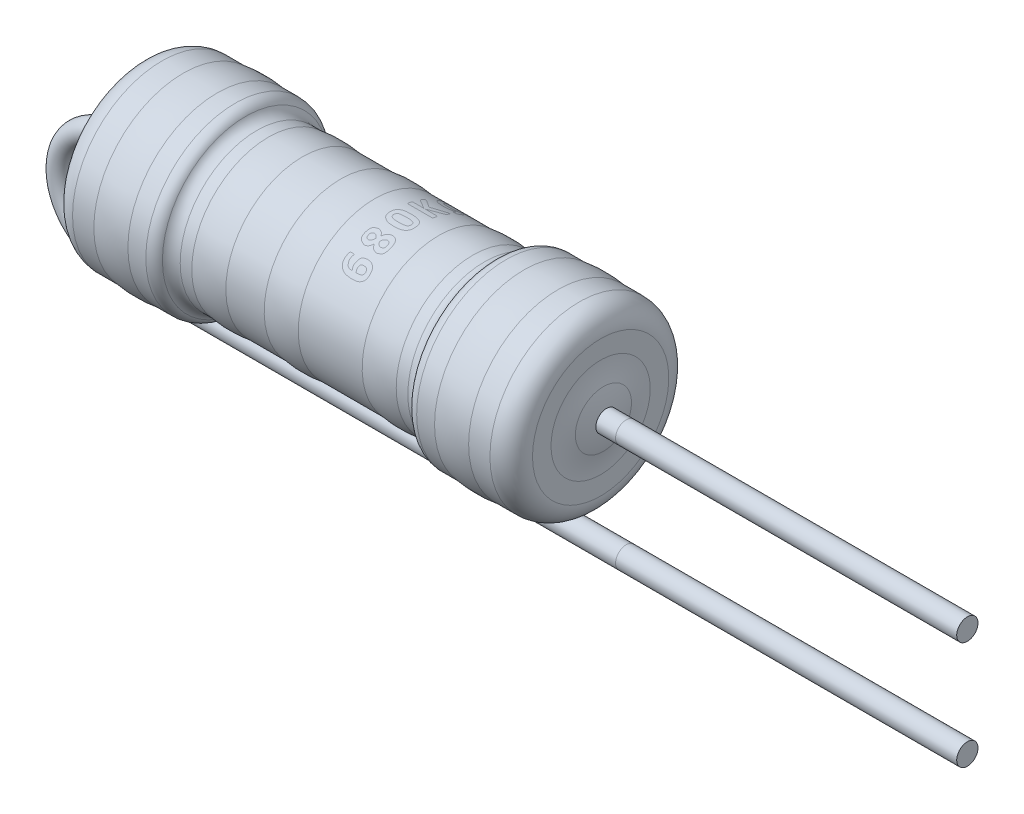
SolidWorks part; units mm, degrees
ref_plane "Front Plane" through (0, 0, 0) normal (0, 0, 1) x (1, 0, 0)
ref_plane "Top Plane" through (0, 0, 0) normal (0, 1, 0) x (1, 0, 0)
ref_plane "Right Plane" through (0, 0, 0) normal (1, 0, 0) x (0, 0, -1)
sketch "Sketch Set Wire Width" plane through (0, 0, 0) normal (0, 0, 1) x (1, 0, 0)
  line L0 (0, 0) -> (6, 0)
  line L1 (6, -2.54) -> (-6, -2.54)
  line L2 (6, 0) -> (14.0102, 0)
  line L3 (-6, 0) -> (-6, -2.54) construction
  line L4 (-6, 0) -> (-6, -2.54) construction
  line L5 (6, -2.54) -> (6, 0) construction
  line L6 (6, -2.54) -> (14.0102, -2.54)
  line L7 (14.0102, -2.54) -> (14.0102, 0) construction
  line L8 (-6, 0) -> (0, 0)
  arc A0 (-6, 0) -> (-6, -2.54) centre (-6, -1.27) ccw
  dimension "D2" = 2.54
  dimension "D3" = 30
  dimension "D1" = 12
  dimension "D4" = 6
sketch "Sketch Wire Diameter" plane through (0, 0, 0) normal (1, 0, 0) x (0, 0, -1)
  circle A0 centre (0, 0) radius 0.25
  dimension "D1" = 0.5
sweep "SET WIRE LENGTH" add profiles "Sketch Wire Diameter" path "Sketch Set Wire Width"
sketch "Sketch3" plane through (0, 0, 0) normal (0, 0, 1) x (1, 0, 0)
  line L0 (-5.4, 0) -> (5.4, 0)
  line L1 (0, 0) -> (0, 1.8) construction
  line L2 (-2.9, 1.8) -> (2.9, 1.8)
  line L3 (-5.4, 0) -> (-5.4, 1.6)
  line L4 (-4.9, 2.1) -> (-3.18, 2.1)
  line L5 (-2.9, 1.82) -> (-2.9, 1.8)
  line L6 (5.4, 0) -> (5.4, 1.6)
  line L7 (4.9, 2.1) -> (3.18, 2.1)
  line L8 (2.9, 1.82) -> (2.9, 1.8)
  arc A0 (-5.4, 1.6) -> (-4.9, 2.1) centre (-4.9, 1.6) cw
  arc A1 (5.4, 1.6) -> (4.9, 2.1) centre (4.9, 1.6) ccw
  arc A2 (-3.18, 2.1) -> (-2.9, 1.82) centre (-3.18, 1.82) cw
  arc A3 (3.18, 2.1) -> (2.9, 1.82) centre (3.18, 1.82) ccw
  dimension "D5" = 0.5
  dimension "D6" = 0.28
  dimension "D1" = 10.8
  dimension "D2" = 5.8
  dimension "D3" = 1.8
  dimension "D4" = 2.1
revolve "Revolve2" add sketch "Sketch3" angle 360 about L0
fillet "Fillet1" radius 0.3 2 edges at (2.9, 0, 1.8) (-2.9, 0, 1.8)
sketch "Sketch5" plane through (0, 0, 0) normal (0, 0, 1) x (1, 0, 0)
  line L0 (0, 0) -> (2, 0) construction
  line L1 (0, 0) -> (-0.3, 0) construction
  line L2 (-0.3, 0) -> (-2, 0) construction
  line L3 (-2, 0) -> (-4, 0) construction
  line L4 (2, 0) -> (4, 0) construction
  line L5 (-4, 0) -> (-4, 2.1) construction
  line L6 (-0.3, 0) -> (-0.3, 1.8) construction
  line L7 (-2, 0) -> (-2, 1.8) construction
  line L8 (2, 0) -> (2, 1.8) construction
  line L9 (4, 0) -> (4, 2.1) construction
  line L10 (-4, 2.1) -> (-4, 2.13) construction
  line L11 (-4.9, 2.1) -> (-3.18, 2.1) construction
  line L12 (4.9, 2.1) -> (3.18, 2.1) construction
  line L13 (-2.9, 1.8) -> (2.9, 1.8) construction
  line L14 (-2, 1.8) -> (-2, 1.83) construction
  line L17 (-4.4, 2.1) -> (-3.6, 2.1)
  line L19 (-5.4, 0) -> (5.4, 0) construction
  line L22 (-2.4, 1.8) -> (-1.6, 1.8) construction
  line L26 (-0.7, 1.8) -> (0.1, 1.8) construction
  line L30 (1.6, 1.8) -> (2.4, 1.8) construction
  line L34 (3.6, 2.1) -> (4.4, 2.1) construction
  line L36 (-0.3, 1.8) -> (-0.3, 1.83) construction
  line L37 (2, 1.8) -> (2, 1.83) construction
  line L38 (4, 2.1) -> (4, 2.13) construction
  arc A0 (-4.4, 2.1) -> (-3.6, 2.1) centre (-4, -0.5517) cw
  arc A1 (-2.4, 1.8) -> (-1.6, 1.8) centre (-2, -0.8517) cw construction
  arc A2 (-0.7, 1.8) -> (0.1, 1.8) centre (-0.3, -0.8517) cw construction
  arc A3 (1.6, 1.8) -> (2.4, 1.8) centre (2, -0.8517) cw construction
  arc A4 (3.6, 2.1) -> (4.4, 2.1) centre (4, -0.5517) cw construction
  dimension "D3" = 0.8
  dimension "D1" = 4
  dimension "D2" = 4
  dimension "D4" = 0.03
  dimension "D5" = 2
  dimension "D6" = 2
  dimension "D7" = 1.7
revolve "Band 1" add sketch "Sketch5" angle 360 about L2
sketch "Sketch8" plane through (0, 0, 0) normal (0, 0, 1) x (1, 0, 0)
  line L0 (-2.4, 1.8) -> (-1.6, 1.8) construction
  line L1 (-2.4, 1.8) -> (-1.6, 1.8)
  arc A0 (-1.6, 1.8) -> (-2.4, 1.8) centre (-2, -0.8517) ccw construction
  arc A1 (-1.6, 1.8) -> (-2.4, 1.8) centre (-2, -0.8517) ccw
revolve "Band 2" add sketch "Sketch8" angle 360 about L2
sketch "Sketch9" plane through (0, 0, 0) normal (0, 0, 1) x (1, 0, 0)
  line L0 (-0.7, 1.8) -> (0.1, 1.8) construction
  line L1 (-0.7, 1.8) -> (0.1, 1.8)
  arc A0 (0.1, 1.8) -> (-0.7, 1.8) centre (-0.3, -0.8517) ccw construction
  arc A1 (0.1, 1.8) -> (-0.7, 1.8) centre (-0.3, -0.8517) ccw
revolve "Band 3" add sketch "Sketch9" angle 360 about L2
sketch "Sketch10" plane through (0, 0, 0) normal (0, 0, 1) x (1, 0, 0)
  line L0 (1.6, 1.8) -> (2.4, 1.8) construction
  line L1 (1.6, 1.8) -> (2.4, 1.8)
  arc A0 (2.4, 1.8) -> (1.6, 1.8) centre (2, -0.8517) ccw construction
  arc A1 (2.4, 1.8) -> (1.6, 1.8) centre (2, -0.8517) ccw
revolve "Band 4" add sketch "Sketch10" angle 360 about L0
sketch "Sketch11" plane through (0, 0, 0) normal (0, 0, 1) x (1, 0, 0)
  line L0 (3.6, 2.1) -> (4.4, 2.1) construction
  line L1 (3.6, 2.1) -> (4.4, 2.1)
  arc A0 (4.4, 2.1) -> (3.6, 2.1) centre (4, -0.5517) ccw construction
  arc A1 (4.4, 2.1) -> (3.6, 2.1) centre (4, -0.5517) ccw
revolve "Band 5" add sketch "Sketch11" angle 360 about L4
sketch "Sketch12" plane through (0, 0, 0) normal (0, 0, 1) x (1, 0, 0)
  line L0 (-5.35, 0) -> (5.35, 0) construction
  line L1 (-5.35, 1) -> (-5.35, 0)
  line L2 (5.35, 1) -> (5.35, 0)
  line L3 (-5.35, 0) -> (-5.55, 0)
  line L4 (5.35, 0) -> (5.55, 0)
  arc A0 (-5.35, 1) -> (-5.55, 0) centre (-2.95, 0) ccw
  arc A1 (5.35, 1) -> (5.55, 0) centre (2.95, 0) cw
  dimension "D3" = 0.2
  dimension "D4" = 2.6
  dimension "D1" = 10.7
  dimension "D2" = 1
revolve "Revolve10" add sketch "Sketch12" angle 360 about L0
fillet "Fillet2" radius 2 2 edges at (5.4, 0, 0.8703) (-5.4, 0, -0.8703)
ref_plane "Plane2" through (0, 3, 0) normal (0, 1, 0) x (1, 0, 0)
sketch "Sketch13" plane through (0, 3, 0) normal (0, 1, 0) x (1, 0, 0)
  line L0 (0, 0) -> (1.15, 0) construction
  line L1 (1.15, 1.75) -> (1.15, -1.75) construction
  text T0 "680KΩ" font "Calibri" height 0.6
  dimension "D1" = 3.5
  dimension "D2" = 1.15
wrap "Wrap1" sketch "Sketch13" wrap type scribe source sketch "Sketch13" face at (0.1, 1.8, 0)
